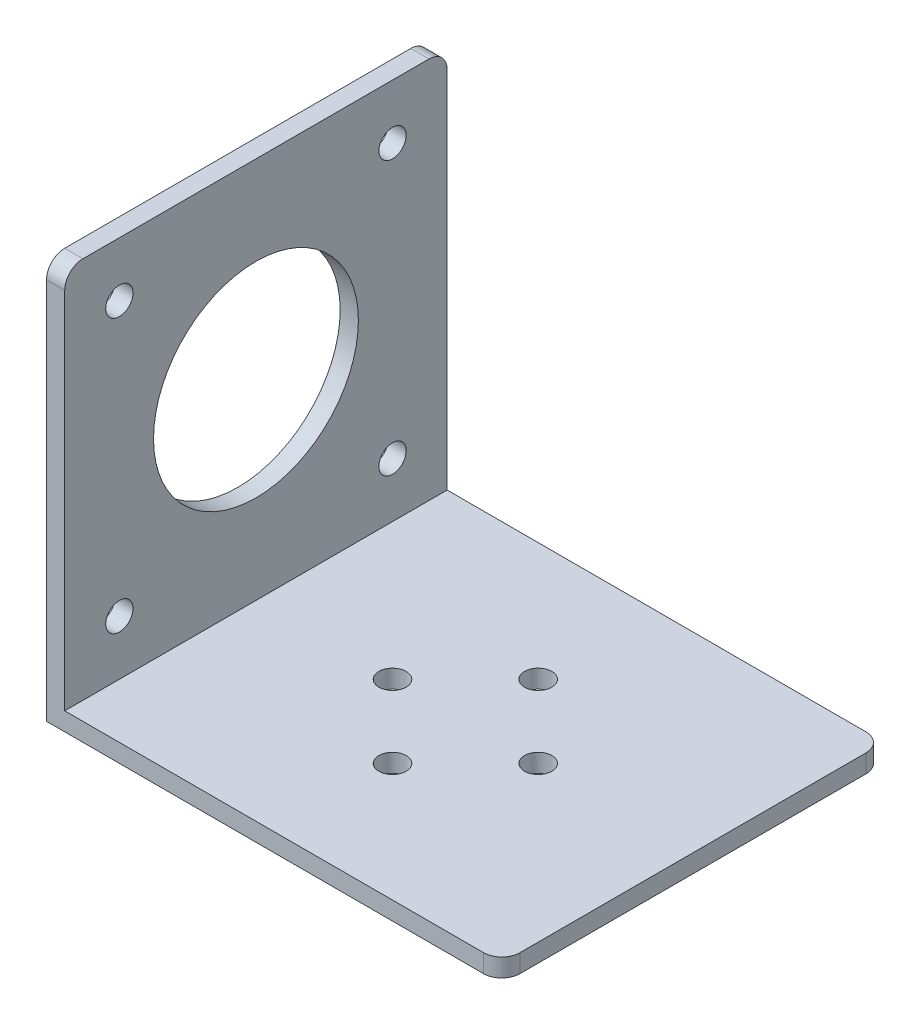
SolidWorks part; units mm, degrees
ref_plane "前视基准面" through (0, 0, 0) normal (0, 0, 1) x (1, 0, 0)
ref_plane "上视基准面" through (0, 0, 0) normal (0, 1, 0) x (1, 0, 0)
ref_plane "右视基准面" through (0, 0, 0) normal (1, 0, 0) x (0, 0, -1)
other "Configuration Table"
sketch "草图1" plane through (0, 0, 0) normal (0, 1, 0) x (1, 0, 0)
  line L1 (-25, -21) -> (25, -21)
  line L2 (-25, -21) -> (-25, 21)
  line L3 (-25, 21) -> (25, 21)
  line L4 (25, -21) -> (25, 21)
  line L5 (-25, -21) -> (25, 21) construction
  line L6 (-25, 21) -> (25, -21) construction
  circle A0 centre (8, 0) radius 1.5
  circle A1 centre (0, 8) radius 1.5
  circle A2 centre (-8, 0) radius 1.5
  circle A3 centre (0, -8) radius 1.5
  point P0 (0, 0)
  dimension "D3" = 3
  dimension "D10" = 3
  dimension "D11" = 3
  dimension "D13" = 3
  dimension "D1" = 42
  dimension "D2" = 50
  dimension "D4" = 16
  dimension "D5" = 16
  dimension "D6" = 0
  dimension "D7" = 0
  dimension "D8" = 13
  dimension "D9" = 25
  dimension "D12" = 17
  dimension "D14" = 21
extrude "凸台-拉伸2" add sketch "草图1" along normal blind 2
sketch "草图2" plane through (-25, 0, 0) normal (-1, 0, 0) x (0, 0, 1)
  line L0 (21, 2) -> (-21, 2)
  line L1 (21, 2) -> (21, 44)
  line L2 (-21, 2) -> (-21, 44)
  line L3 (21, 44) -> (-21, 44)
  circle A0 centre (15, 38) radius 1.5
  circle A1 centre (15, 8) radius 1.5
  circle A2 centre (-15, 8) radius 1.5
  circle A3 centre (-15, 38) radius 1.5
  circle A4 centre (0, 23) radius 11.25
  dimension "D2" = 3
  dimension "D3" = 3
  dimension "D4" = 3
  dimension "D5" = 3
  dimension "D14" = 22.5
  dimension "D1" = 42
  dimension "D6" = 30
  dimension "D7" = 30
  dimension "D8" = 30
  dimension "D9" = 6
  dimension "D10" = 6
  dimension "D11" = 0
  dimension "D12" = 0
  dimension "D13" = 0
  dimension "D15" = 21
  dimension "D16" = 21
extrude "凸台-拉伸3" add sketch "草图2" against normal blind 2
fillet "圆角1" radius 2 1 edges at (-24, 44, 21)
fillet "圆角2" radius 2 1 edges at (-24, 44, -21)
fillet "圆角3" radius 2 2 edges at (25, 1, -21) (25, 1, 21)
